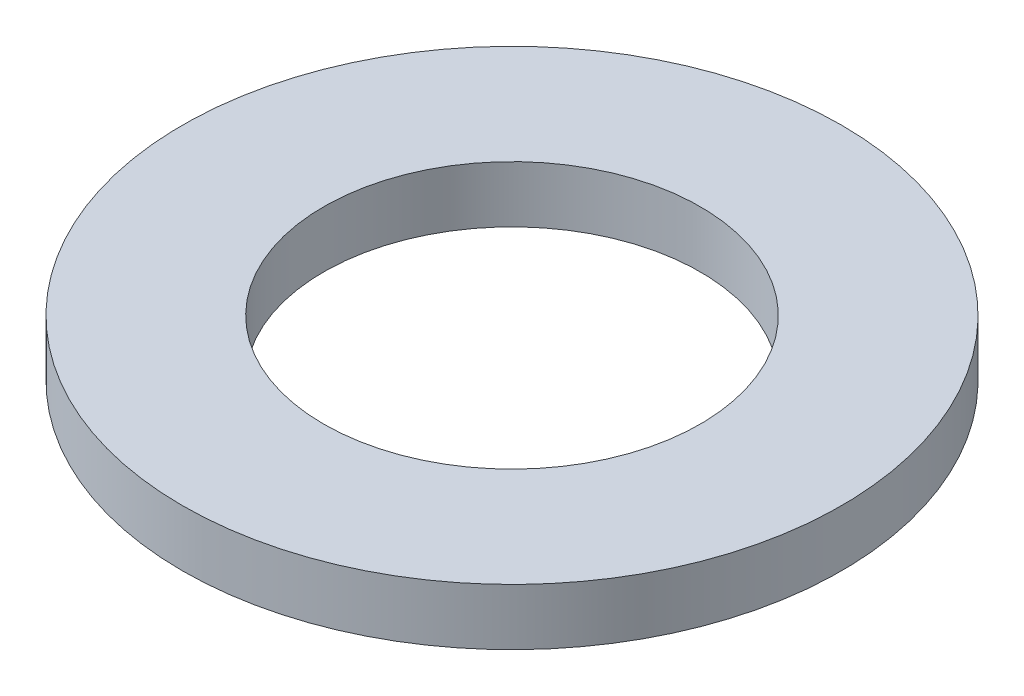
SolidWorks part; units mm, degrees
ref_plane "Front Plane" through (0, 0, 0) normal (0, 0, 1) x (1, 0, 0)
ref_plane "Top Plane" through (0, 0, 0) normal (0, 1, 0) x (1, 0, 0)
ref_plane "Right Plane" through (0, 0, 0) normal (1, 0, 0) x (0, 0, -1)
sketch "Sketch1" plane through (0, 0, 0) normal (0, 1, 0) x (1, 0, 0)
  circle A0 centre (0, 0) radius 35
  circle A1 centre (0, 0) radius 20
  dimension "D1" = 70
  dimension "D2" = 40
extrude "Boss-Extrude1" add sketch "Sketch1" along normal blind 6
